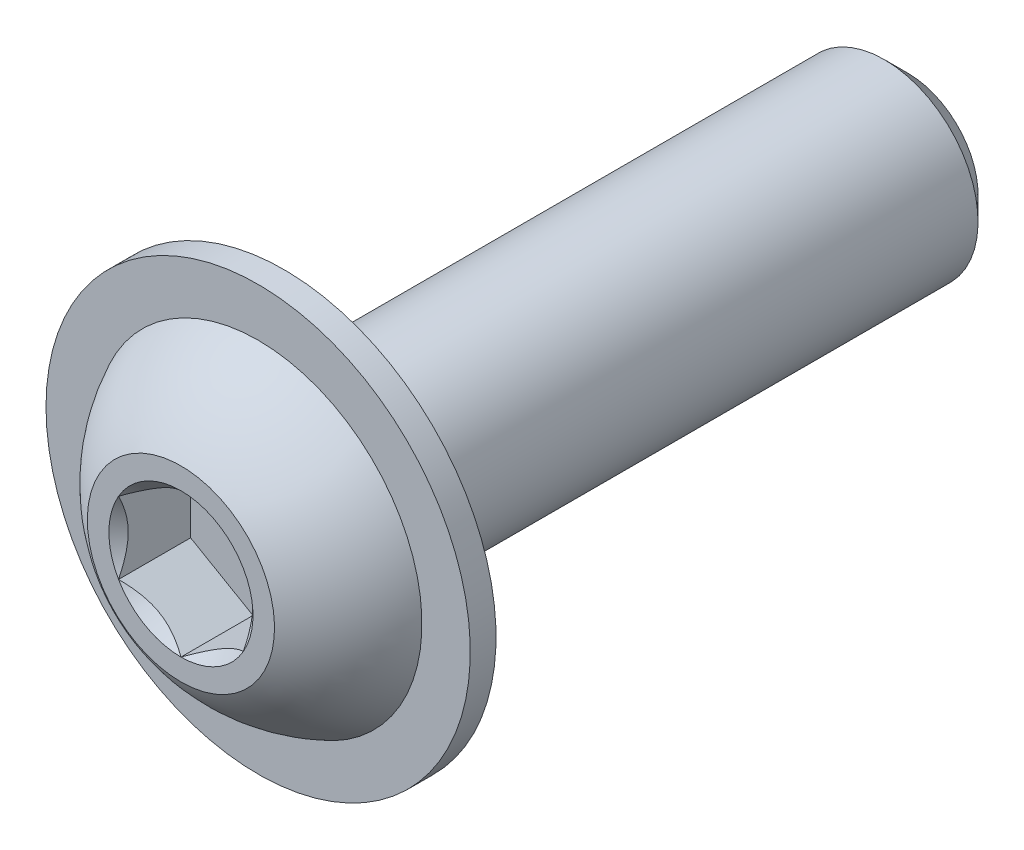
SolidWorks part; units mm, degrees
material "AISI 304"
ref_plane "Front" through (0, 0, 0) normal (0, 0, 1) x (1, 0, 0)
ref_plane "Top" through (0, 0, 0) normal (0, 1, 0) x (1, 0, 0)
ref_plane "Right" through (0, 0, 0) normal (1, 0, 0) x (0, 0, -1)
sketch "Sketch1" plane through (0, 0, 0) normal (1, 0, 0) x (0, 0, -1)
  line L2 (3.3, 3) -> (23.3, 3)
  line L3 (23.3, 3) -> (23.3, 0)
  line L4 (23.3, 0) -> (3.3, 0)
  line L6 (2.475, 5.25) -> (3.3, 5.25) construction
  line L7 (23.3, 3) -> (23.3, -3) construction
  line L8 (0, 0) -> (3.3, 0) construction
  line L9 (3.3, 5.25) -> (3.3, -5.25) construction
  line L11 (3.3, 3) -> (3.3, 0)
  line L13 (0, 2) -> (0, -2) construction
  line L14 (0, 2) -> (0, 3) construction
  line L15 (2.475, 5.25) -> (2.475, 6.8) construction
  line L16 (2.475, 6.8) -> (3.3, 6.8) construction
  line L17 (3.3, 6.8) -> (3.3, 5.25) construction
  line L18 (3.3, 6.8) -> (3.3, -6.8) construction
  arc A3 (0, 3) -> (2.475, 5.25) centre (4.9875, 0) cw construction
  dimension "D1" = 0.825
revolve "Revolve1" add sketch "Sketch1" angle 360 mid plane about L4
sketch "Sketch3" plane through (0, 0, -23.3) normal (0, 0, -1) x (-1, 0, 0)
  circle A0 centre (0, 0) radius 3
curve "Helix/Spiral1" pitch 1 height 21 turns 21
sketch "Sketch2" plane through (0, 0, 0) normal (1, 0, 0) x (0, 0, -1)
  line L0 (23.3, 3) -> (24.175, 3)
  line L1 (24.175, 3) -> (23.8, 2.3505)
  line L2 (23.8, 2.3505) -> (23.675, 2.3505)
  line L3 (23.675, 2.3505) -> (23.3, 3)
  line L4 (23.4875, 2.6752) -> (23.9875, 2.6752) construction
  dimension "D1" = 60
  dimension "D2" = 0.125
  dimension "D3" = 0.5
chamfer "Chamfer1" distance 0.75 angle 45 1 edges at (0, 3, -23.3)
sweep "Cut-Sweep1" [suppressed] cut profiles "Sketch2" path "Helix/Spiral1"
sketch "Sketch7" plane through (0, 0, 0) normal (1, 0, 0) x (0, 0, -1)
  line L6 (2.475, 5.25) -> (3.3, 5.25) construction
  line L8 (0, 0) -> (3.3, 0) construction
  line L11 (3.3, 5.25) -> (3.3, -5.25) construction
  line L12 (2.475, 5.25) -> (3.3, 5.25)
  line L13 (0, 0) -> (3.3, 0)
  line L14 (0, 2) -> (0, -2) construction
  line L15 (3.3, 5.25) -> (3.3, 0)
  line L16 (0, 3) -> (0, 0)
  arc A2 (2.475, 5.25) -> (0, 3) centre (4.9875, 0) ccw construction
  arc A3 (2.475, 5.25) -> (0, 3) centre (4.9875, 0) ccw
revolve "Revolve2" add sketch "Sketch7" angle 360 mid plane about L13
sketch "Sketch11" plane through (0, 0, -3.3) normal (0, 0, -1) x (-1, 0, 0)
  circle A0 centre (0, 0) radius 6.8
extrude "Boss-Extrude3" add sketch "Sketch11" against normal up to vertex (0.825 mm away) up to point (0, 5.25, -2.475)
sketch "Sketch5" plane through (0, 0, 0) normal (0, 0, 1) x (1, 0, 0)
  line L1 (2, -1.1547) -> (2, 1.1547)
  line L2 (2, 1.1547) -> (0, 2.3094)
  line L3 (0, 2.3094) -> (-2, 1.1547)
  line L4 (-2, 1.1547) -> (-2, -1.1547)
  line L5 (-2, -1.1547) -> (0, -2.3094)
  line L6 (0, -2.3094) -> (2, -1.1547)
  circle A0 centre (0, 0) radius 2 construction
extrude "Cut-Extrude2" cut sketch "Sketch5" against normal blind 2.31
sketch "Sketch6" plane through (0, 0, 0) normal (0, 0, 1) x (1, 0, 0)
  circle A0 centre (0, 0) radius 2.3094
extrude "Cut-Extrude3" cut sketch "Sketch6" against normal blind 2.31 draft 45
sketch "Sketch9" [suppressed] plane through (0, 0, -3.3) normal (0, 0, 1) x (1, 0, 0)
  circle A2 centre (0, 0) radius 3
extrude "Boss-Extrude2" [suppressed] add sketch "Sketch9" against normal offset from surface (6.35 mm away) 31.75
sketch "Sketch10" plane through (0, 0, 0) normal (1, 0, 0) x (0, 0, -1)
  line L0 (23.3, 3) -> (23.3, -3) construction
  point P0 (21.8, -3)
  dimension "D1" = 1.5
equation "\"D3@Helix/Spiral1\" = \"Lg@Sketch1\" + \"D4@Helix/Spiral1\""
equation "\"D2@Sketch2\" = \"D4@Helix/Spiral1\" * .125"
equation "\"D3@Sketch2\" = \"D4@Helix/Spiral1\" * .5"
equation "\"D1@Chamfer1\" = \"D4@Helix/Spiral1\" * .75"
equation "\"D1@Cut-Extrude2\" = \"Head Ht@Sketch1\" * .7"
equation "\"D1@Sketch1\" = \"Head Ht@Sketch1\" * .25"
equation "\"D1@Sketch10\" = \"D4@Helix/Spiral1\" * 1.5"
equation "\"D1@Cut-Extrude3\" = \"D1@Cut-Extrude2\""
